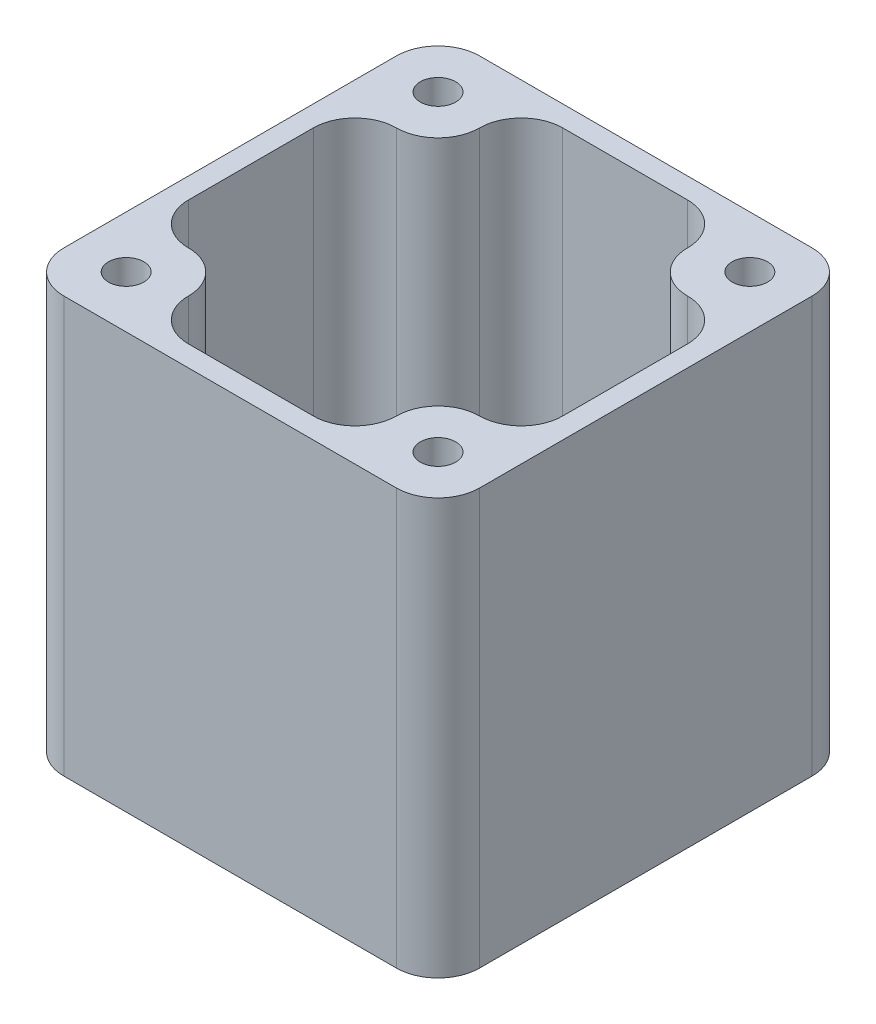
SolidWorks part; units mm, degrees
ref_plane "Front Plane" through (0, 0, 0) normal (0, 0, 1) x (1, 0, 0)
ref_plane "Top Plane" through (0, 0, 0) normal (0, 1, 0) x (1, 0, 0)
ref_plane "Right Plane" through (0, 0, 0) normal (1, 0, 0) x (0, 0, -1)
sketch "Sketch1" plane through (0, 0, 0) normal (0, 1, 0) x (1, 0, 0)
  line L1 (-20, 20) -> (20, 20)
  line L2 (-20, 20) -> (-20, -20)
  line L3 (-20, -20) -> (20, -20)
  line L4 (20, 20) -> (20, -20)
  line L5 (-20, 20) -> (20, -20) construction
  line L6 (-20, -20) -> (20, 20) construction
  line L7 (-15, -15) -> (15, -15) construction
  line L8 (-15, -15) -> (-15, 15) construction
  line L9 (-15, 15) -> (15, 15) construction
  line L10 (15, -15) -> (15, 15) construction
  line L11 (-15, -15) -> (15, 15) construction
  line L12 (-15, 15) -> (15, -15) construction
  circle A0 centre (15, 15) radius 1.7
  circle A1 centre (-15, 15) radius 1.7
  circle A2 centre (-15, -15) radius 1.7
  circle A3 centre (15, -15) radius 1.7
  point P0 (0, 0)
  point P6 (0, 0)
  dimension "D3" = 3.4
  dimension "D1" = 40
  dimension "D2" = 30
extrude "Boss-Extrude1" add sketch "Sketch1" along normal blind 40 contours A1 | A0 | A2 | A3 | L1 L4 L3 L2 region at (15, 0, -15) region at (-15, 0, -15) region at (-15, 0, 15) region at (15, 0, 15)
sketch "Sketch2" plane through (0, 40, 0) normal (0, 1, 0) x (1, 0, 0)
  line L1 (-18, -10) -> (18, -10)
  line L2 (-18, -10) -> (-18, 10)
  line L3 (-18, 10) -> (18, 10)
  line L4 (18, -10) -> (18, 10)
  line L5 (-18, -10) -> (18, 10) construction
  line L6 (-18, 10) -> (18, -10) construction
  point P0 (0, 0)
  dimension "D1" = 20
  dimension "D2" = 36
extrude "Cut-Extrude1" cut sketch "Sketch2" against normal blind 38
ref_axis "Axis1" through (0, 42, 0) along (0, -1, 0)
pattern_circular "CirPattern1" count 2 every 90 about axis through (0, 42, 0) along (0, -1, 0) of "Cut-Extrude1"
fillet "Fillet1" radius 4 16 edges at (-18, 21, 10) (-10, 21, 10) (-10, 21, 18) (10, 21, 18) (10, 21, 10) (18, 21, 10) (18, 21, -10) (10, 21, -10) (10, 21, -18) (-10, 21, -18) (-18, 21, -10) (-10, 21, -10) (-20, 20, -20) (20, 20, -20) (20, 20, 20) (-20, 20, 20)
